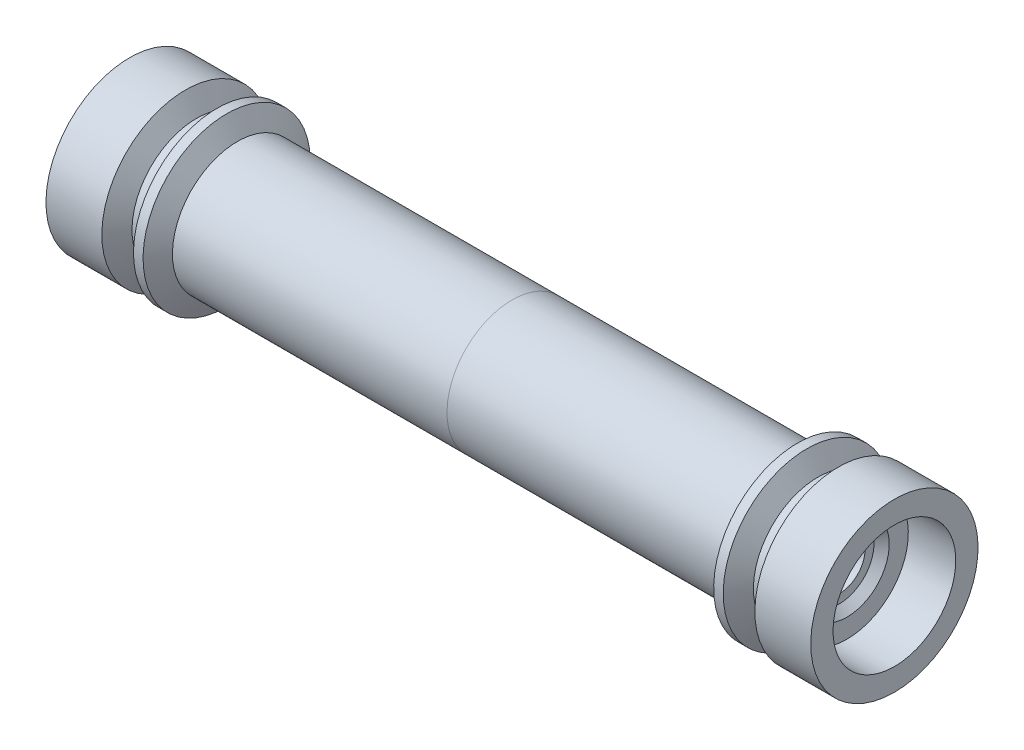
SolidWorks part; units mm, degrees
ref_plane "Front Plane" through (0, 0, 0) normal (0, 0, 1) x (1, 0, 0)
ref_plane "Top Plane" through (0, 0, 0) normal (0, 1, 0) x (1, 0, 0)
ref_plane "Right Plane" through (0, 0, 0) normal (1, 0, 0) x (0, 0, -1)
sketch "Sketch2" plane through (0, 0, 0) normal (0, 0, 1) x (1, 0, 0)
  line L0 (0, 0) -> (0, 28.4375) construction
  line L1 (-25.4, 4.075) -> (-22.25, 4.075) construction
  line L2 (-25.4, 4.075) -> (-25.4, -4.075) construction
  line L3 (-25.4, -4.075) -> (-22.25, -4.075) construction
  line L4 (-22.25, 4.075) -> (-22.25, -4.075) construction
  line L5 (-25.4, 4.075) -> (-22.25, -4.075) construction
  line L6 (-25.4, -4.075) -> (-22.25, 4.075) construction
  line L7 (22.25, 4.5) -> (41.3332, 4.5) construction
  line L8 (22.25, 4.5) -> (22.25, -4.5) construction
  line L9 (22.25, -4.5) -> (41.3332, -4.5) construction
  line L10 (41.3332, 4.5) -> (41.3332, -4.5) construction
  line L11 (22.25, 4.5) -> (41.3332, -4.5) construction
  line L12 (22.25, -4.5) -> (41.3332, 4.5) construction
  line L13 (-25.4, 0) -> (41.3332, 0) construction
  line L14 (-25.4, 5.5562) -> (-21.6882, 5.5562)
  line L21 (-18.2369, 4.318) -> (0, 4.318)
  line L22 (-25.4, 5.5562) -> (-25.4, 4.075)
  line L23 (-25.4, 4.075) -> (-22.25, 4.075)
  line L24 (-22.25, 4.075) -> (-22.25, 0)
  line L25 (-22.25, 0) -> (0, 0)
  line L26 (0, 0) -> (0, 4.318)
  line L27 (-33.5594, -5.5562) -> (-33.5594, 5.5562) construction
  line L28 (-21.6882, 5.5562) -> (-20.955, 4.2862)
  line L29 (-20.955, 4.2862) -> (-20.32, 4.2862)
  line L30 (-25.4, 5.5562) -> (25.4, 5.5562) construction
  line L31 (0, 1.6) -> (-12.5, 1.6)
  line L32 (-12.5, 1.6) -> (-14.1, 0)
  line L33 (-12.5, 1.6) -> (-12.5, -1.6) construction
  line L34 (-12.5, 1.6) -> (12.5, 1.6) construction
  line L35 (-22.25, 1.7145) -> (-15.575, 1.7145)
  line L36 (-15.575, 1.7145) -> (-15.575, 0)
  line L37 (-22.25, 2.805) -> (-21.742, 2.297)
  line L38 (-15.575, 1.7145) -> (-28.575, 1.7145) construction
  line L39 (-15.575, 1.7145) -> (-15.575, -1.7145) construction
  line L40 (-15.575, -1.7145) -> (-28.575, -1.7145) construction
  line L41 (-28.575, 1.7145) -> (-28.575, -1.7145) construction
  line L42 (-21.742, 2.297) -> (-21.742, 0)
  line L46 (-20.32, 4.2862) -> (-19.5868, 5.5562)
  line L47 (-19.5868, 5.5562) -> (-18.9518, 5.5562)
  line L48 (-18.9518, 5.5562) -> (-18.2369, 4.318)
  line L49 (-20.6375, 4.2862) -> (-20.6375, 8.7882) construction
  line L50 (-20.6375, 8.7882) -> (20.6375, 8.7882) construction
  point P0 (-23.825, 0)
  point P5 (31.7916, 0)
  point P27 (-33.5594, 0)
  point P29 (-12.5, 0)
  point P33 (0, 8.7882)
  point P36 (0, 1.6)
  point P48 (-15.575, 0)
  point P51 (0, 5.5562)
  dimension "D3" = 4.318
  dimension "D4" = 11.1125
  dimension "D5" = 8.15
  dimension "D6" = 60
  dimension "D7" = 0.635
  dimension "D8" = 60
  dimension "D9" = 41.275
  dimension "D10" = 1.27
  dimension "D11" = 50.8
  dimension "D12" = 0.635
  dimension "D13" = 45
  dimension "D14" = 25
  dimension "D15" = 3.2
  dimension "D16" = 3.429
  dimension "D17" = 3.175
  dimension "D18" = 1.27
  dimension "D19" = 0.508
  dimension "D20" = 45
  dimension "D21" = 13
  dimension "D22" = 3.15
revolve "Revolve1" add sketch "Sketch2" angle 360 about L13 region at (-12.3482, 3.069, 0)
mirror "Mirror1" about plane through (0, 0, 0) normal (1, 0, 0) of bodies 101
chamfer "Chamfer1" distance 0.508 angle 45 1 edges at (-25.4, -4.075, 0)
